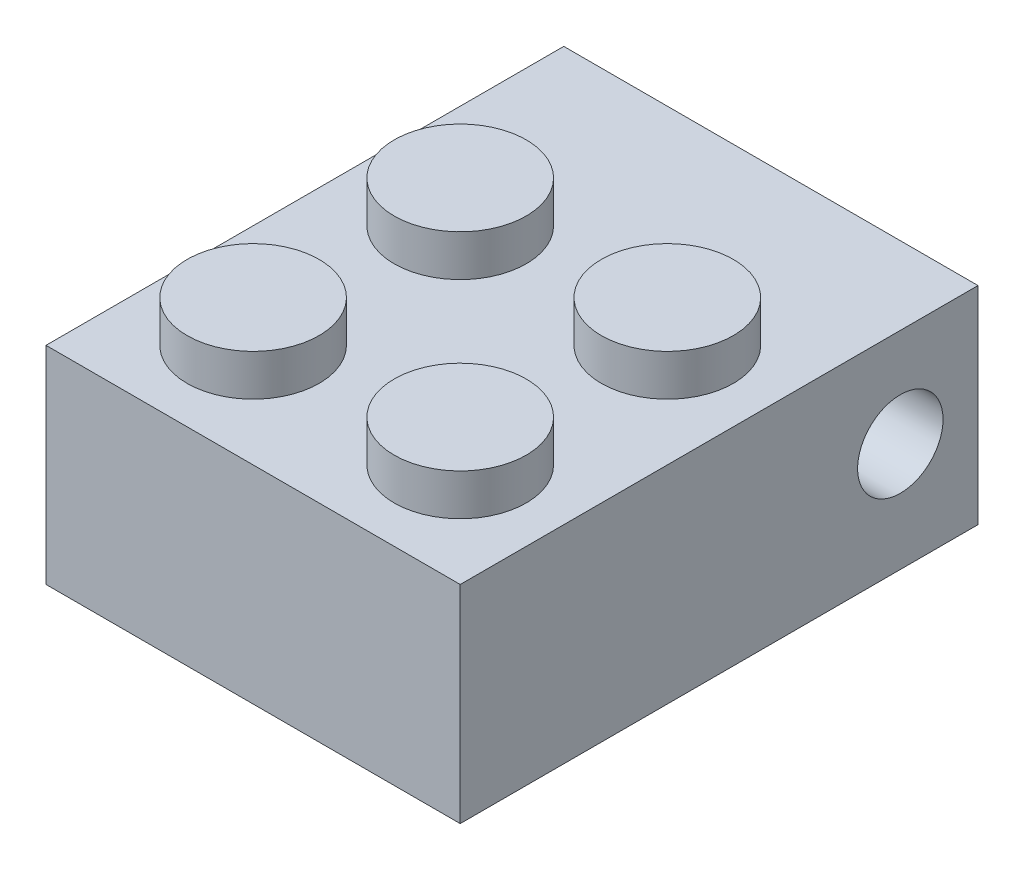
SolidWorks part; units mm, degrees
ref_plane "Front Plane" through (0, 0, 0) normal (0, 0, 1) x (1, 0, 0)
ref_plane "Top Plane" through (0, 0, 0) normal (0, 1, 0) x (1, 0, 0)
ref_plane "Right Plane" through (0, 0, 0) normal (1, 0, 0) x (0, 0, -1)
sketch "Sketch1" plane through (76, 0, 0) normal (1, 0, 0) x (0, 0, -1)
  line L0 (41.2674, -14.7525) -> (-6.7326, -14.7525) construction
  line L1 (41.2674, -14.7525) -> (-6.7326, -14.7525)
  line L2 (41.2674, -14.7525) -> (45.2674, -14.7525)
  line L3 (45.2674, -14.7525) -> (45.2674, -6.7525)
  line L4 (45.2674, -6.7525) -> (25.2674, -6.7525)
  line L5 (25.2674, -6.7525) -> (25.2674, -14.7525)
  arc A0 (42.2674, -11.8775) -> (42.2674, -9.2275) centre (42.2674, -10.5525) ccw construction
  arc A1 (42.2674, -11.8775) -> (42.2674, -9.2275) centre (42.2674, -10.5525) ccw construction
  circle A2 centre (42.2674, -10.5525) radius 1.65
  line M3 (41.2674, -14.7525) -> (-6.7326, -14.7525)
  dimension "D3" = 3.3
  dimension "D1" = 16
  dimension "D2" = 8
  dimension "D4" = 4
extrude "Boss-Extrude1" add sketch "Sketch1" against normal blind 16 contours L4 L5 L2 L3 A2 M3 region at (76, -10.7638, -34.872)
sketch "Sketch2" plane through (0, -6.7525, 0) normal (0, 1, 0) x (1, 0, 0)
  circle A0 centre (64, 29.2674) radius 2.4 construction
  circle A1 centre (72, 29.2674) radius 2.4 construction
  circle A2 centre (72, 37.2674) radius 2.4 construction
  circle A3 centre (64, 37.2674) radius 2.4 construction
  circle A4 centre (64, 29.2674) radius 2.4 construction
  circle A5 centre (72, 29.2674) radius 2.4 construction
  circle A6 centre (72, 37.2674) radius 2.4 construction
  circle A7 centre (64, 37.2674) radius 2.4 construction
  circle A8 centre (64, 37.2674) radius 2.55
  circle A10 centre (72, 37.2674) radius 2.55
  circle A12 centre (72, 29.2674) radius 2.55
  circle A14 centre (64, 29.2674) radius 2.55
  dimension "D1" = 0.15
extrude "Boss-Extrude2" add sketch "Sketch2" along normal blind 1.6
extrude "Cut-Extrude1" cut sketch "Sketch2<2>" along normal blind 1.7 from surface contours A12 | A14 | A8 | A10 region at (64, -6.7525, -37.2674) region at (72, -6.7525, -37.2674) region at (72, -6.7525, -29.2674) region at (64, -6.7525, -29.2674) starting at face at (68, -14.7525, -35.2674)
sketch "Sketch2<2>" plane through (0, -6.7525, 0) normal (0, 1, 0) x (1, 0, 0) same geometry as "Sketch2"
